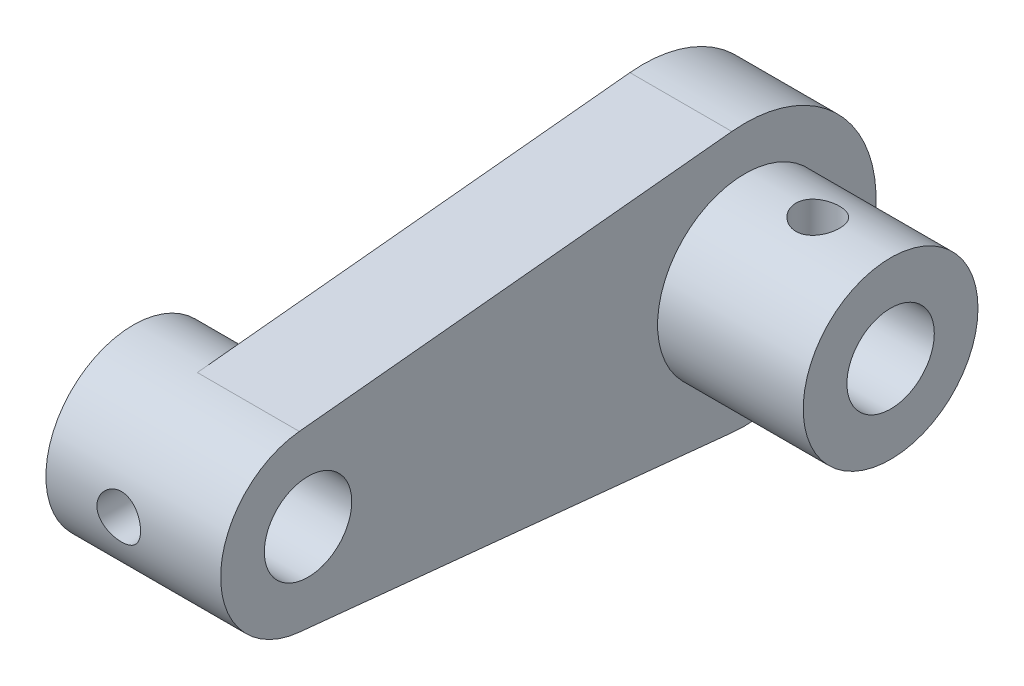
SolidWorks part; units mm, degrees
material "Custom Plastic"
ref_plane "Front Plane" through (0, 0, 0) normal (1, 0, 0) x (0, 1, 0)
ref_plane "Top Plane" through (0, 0, 0) normal (0, 0, 1) x (0, 1, 0)
ref_plane "Right Plane" through (0, 0, 0) normal (0, 1, 0) x (-1, 0, 0)
sketch "Sketch1" plane through (0, 0, 0) normal (1, 0, 0) x (0, 1, 0)
  line L0 (-5.9699, 30.6) -> (-8.9549, 0.9)
  line L1 (8.9549, 0.9) -> (5.9699, 30.6)
  circle A0 centre (0, 0) radius 3
  arc A1 (-8.9549, 0.9) -> (8.9549, 0.9) centre (0, 0) ccw
  circle A2 centre (0, 30) radius 3
  arc A3 (5.9699, 30.6) -> (-5.9699, 30.6) centre (0, 30) ccw
  dimension "D1" = 6
  dimension "D2" = 18
  dimension "D3" = 6
  dimension "D4" = 12
  dimension "D5" = 30
extrude "Boss-Extrude1" add sketch "Sketch1" along normal blind 7
sketch "Sketch2" plane through (7, 0, 0) normal (1, 0, 0) x (0, 1, 0)
  circle A0 centre (0, 0) radius 3
  circle A1 centre (0, 0) radius 6
  circle A2 centre (0, 30) radius 3
  circle A3 centre (0, 30) radius 6
  circle M5 centre (0, 0) radius 3
  arc M6 (5.9699, 30.6) -> (-5.9699, 30.6) centre (0, 30) ccw
  circle M10 centre (0, 30) radius 3
  dimension "D1" = 6
  dimension "D2" = 12
  dimension "D3" = 12
extrude "Boss-Extrude2" add sketch "Sketch2" against normal blind 12 contours A3 M6 M10 region at (7, -0.2919, 24.177)
extrude "Boss-Extrude3" add sketch "Sketch2<4>" along normal blind 10 contours A1 M5 region at (7, -5.8303, 0)
sketch "Sketch2<4>" plane through (7, 0, 0) normal (1, 0, 0) x (0, 1, 0) same geometry as "Sketch2"
sketch "Sketch4" plane through (0, 0, 0) normal (0, 1, 0) x (-1, 0, 0)
  line L0 (-17, 6) -> (-17, -6) construction
  circle A1 centre (-12, 0) radius 1.5
  dimension "D1" = 5
  dimension "D2" = 3
extrude "Cut-Extrude1" cut sketch "Sketch4" against normal through all both and the other way through all
ref_plane "Plane1" through (0, 0, 30) normal (0, 0, 1) x (0, 1, 0)
sketch "Sketch6" plane through (0, 0, 30) normal (0, 0, 1) x (0, 1, 0)
  circle A0 centre (0, 0) radius 1.5
  dimension "D1" = 3
extrude "Cut-Extrude2" cut sketch "Sketch6" along normal through all
